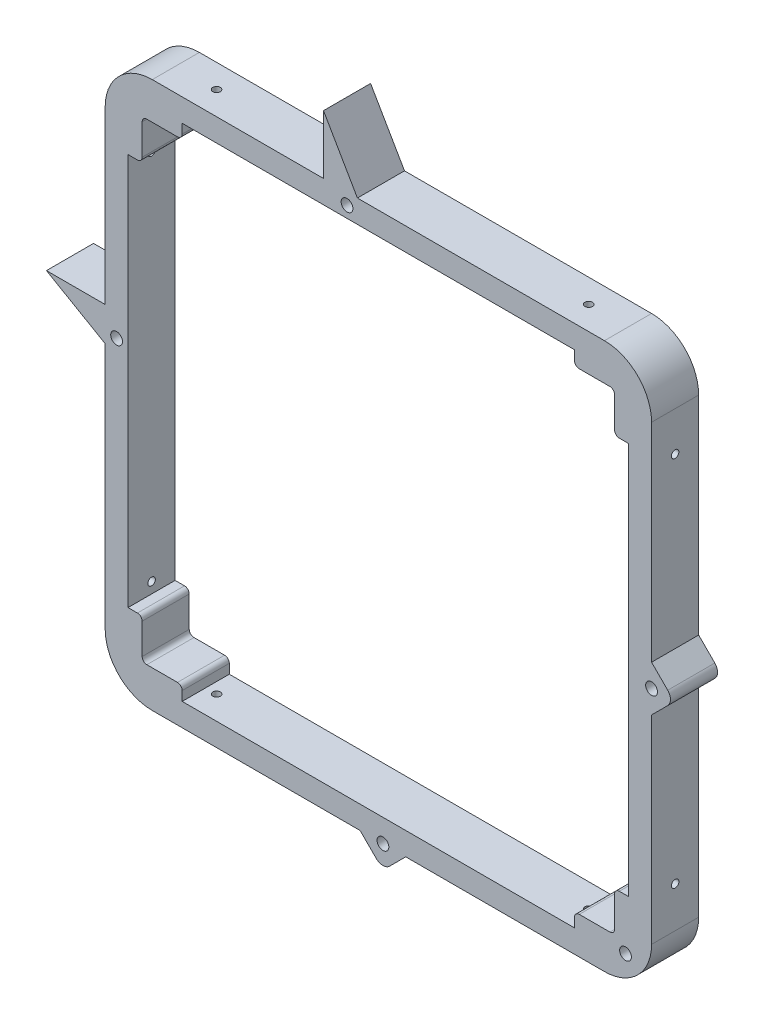
SolidWorks part; units mm, degrees
material "Nylon 101"
ref_plane "Front Plane" through (0, 0, 0) normal (0, 0, 1) x (1, 0, 0)
ref_plane "Top Plane" through (0, 0, 0) normal (0, 1, 0) x (1, 0, 0)
ref_plane "Right Plane" through (0, 0, 0) normal (1, 0, 0) x (0, 0, -1)
sketch "Sketch1" plane through (0, 0, 0) normal (0, 0, 1) x (1, 0, 0)
  line L13 (50.0019, -50.0019) -> (58, -58) construction
  line L14 (53, -41.5) -> (50.0019, -41.5)
  line L17 (41.5, -53) -> (41.5, -50.0019)
  line L18 (50.0019, -44.9586) -> (53, -44.9586)
  line L20 (53, -44.9586) -> (53, -53)
  line L23 (53, -53) -> (44.9586, -53)
  line L24 (44.9586, -53) -> (44.9586, -50.0019)
  line L25 (50.0019, -41.5) -> (50.0019, -50.0019)
  line L27 (50.0019, -50.0019) -> (41.5, -50.0019)
  line L35 (-41.5, 53) -> (41.5, 53)
  line L37 (50.0019, -50.0019) -> (50.0019, -41.5)
  line L38 (41.5, -50.0019) -> (50.0019, -50.0019)
  line L39 (53, -44.9586) -> (50.0019, -44.9586)
  line L40 (53, -53) -> (53, -44.9586)
  line L42 (44.9586, -53) -> (53, -53)
  line L43 (44.9586, -50.0019) -> (44.9586, -53)
  line L44 (53, -41.5) -> (50.0019, -41.5)
  line L45 (41.5, -53) -> (41.5, -50.0019)
  line L47 (53, -41.5) -> (53, 41.5)
  line L50 (41.5, -53) -> (-41.5, -53)
  line L52 (-41.5, -53) -> (-41.5, -50.0019)
  line L53 (-53, -41.5) -> (-50.0019, -41.5)
  line L54 (-44.96, -50.0019) -> (-44.96, -53)
  line L55 (-44.96, -53) -> (-53, -53)
  line L57 (-53, -53) -> (-53, -44.96)
  line L58 (-53, -44.96) -> (-50.0019, -44.96)
  line L59 (-41.5, -50.0019) -> (-50.0019, -50.0019)
  line L60 (-50.0019, -50.0019) -> (-50.0019, -41.5)
  line L61 (-53, -41.5) -> (-53, 41.5)
  line L63 (58, 58) -> (58, -58)
  line L65 (-50.0019, -50.0019) -> (-41.5, -50.0019)
  line L66 (-50.0019, -41.5) -> (-50.0019, -50.0019)
  line L67 (-44.96, -53) -> (-44.96, -50.0019)
  line L68 (-53, -53) -> (-44.96, -53)
  line L70 (-53, -44.96) -> (-53, -53)
  line L71 (-50.0019, -44.96) -> (-53, -44.96)
  line L72 (-41.5, -53) -> (-41.5, -50.0019)
  line L73 (-53, -41.5) -> (-50.0019, -41.5)
  line L75 (58, -58) -> (-58, -58)
  line L77 (-50.0019, -50.0019) -> (-58, -58) construction
  line L79 (-58, -58) -> (-58, 58)
  line L81 (-53, 41.5) -> (-50.0019, 41.5)
  line L82 (-41.5, 53) -> (-41.5, 50.0019)
  line L83 (-50.0019, 44.96) -> (-53, 44.96)
  line L84 (-53, 44.96) -> (-53, 53)
  line L86 (-53, 53) -> (-44.96, 53)
  line L87 (-44.96, 53) -> (-44.96, 50.0019)
  line L88 (-50.0019, 41.5) -> (-50.0019, 50.0019)
  line L89 (-50.0019, 50.0019) -> (-41.5, 50.0019)
  line L90 (-58, 58) -> (58, 58)
  line L94 (-50.0019, 50.0019) -> (-50.0019, 41.5)
  line L95 (-41.5, 50.0019) -> (-50.0019, 50.0019)
  line L96 (-53, 44.96) -> (-50.0019, 44.96)
  line L97 (-53, 53) -> (-53, 44.96)
  line L99 (-44.96, 53) -> (-53, 53)
  line L100 (-44.96, 50.0019) -> (-44.96, 53)
  line L101 (-53, 41.5) -> (-50.0019, 41.5)
  line L102 (-41.5, 53) -> (-41.5, 50.0019)
  line L106 (-50.0019, 50.0019) -> (-58, 58) construction
  line L110 (41.5, 53) -> (41.5, 50.0019)
  line L111 (53, 41.5) -> (50.0019, 41.5)
  line L112 (44.9586, 50.0019) -> (44.9586, 53)
  line L113 (44.9586, 53) -> (53, 53)
  line L115 (53, 53) -> (53, 44.96)
  line L116 (53, 44.96) -> (50.0019, 44.96)
  line L117 (41.5, 50.0019) -> (50.0019, 50.0019)
  line L118 (50.0019, 50.0019) -> (50.0019, 41.5)
  line L123 (50.0019, 50.0019) -> (41.5, 50.0019)
  line L124 (50.0019, 41.5) -> (50.0019, 50.0019)
  line L125 (44.9586, 53) -> (44.9586, 50.0019)
  line L126 (53, 53) -> (44.9586, 53)
  line L128 (53, 44.96) -> (53, 53)
  line L129 (50.0019, 44.96) -> (53, 44.96)
  line L130 (41.5, 53) -> (41.5, 50.0019)
  line L131 (53, 41.5) -> (50.0019, 41.5)
  line L135 (50.0019, 50.0019) -> (58, 58) construction
  point P2 (0, 58)
  point P4 (0, 53)
  point P6 (0, -53)
  point P7 (0, -58)
  point P10 (53, 0)
  point P11 (-53, 0)
  point P16 (-58, 0)
  point P17 (58, 0)
  dimension "D1" = 106
  dimension "D2" = 5
  dimension "D3" = 2.9981
extrude "base" add sketch "Sketch1" along normal mid plane 10 contours L20 L13 L14 L25 L18 | L13 L23 L24 L27 L17 | L13 L27 L24 L23 | L25 L13 L20 L18 | L117 L118 L116 L115 L113 L112 | L88 L89 L87 L86 L84 L83 | L59 L60 L58 L57 L55 L54 region at (51.5009, -45.0723, 0) region at (50.1156, 47.4809, 0) region at (-45.0737, -51.5009, 0) region at (-47.4809, 50.1156, 0) region at (56.3595, 0, 0)
ref_plane "Plane3" through (0, 0, 15) normal (0, 0, 1) x (1, 0, 0)
sketch "Sketch7" plane through (0, 0, 15) normal (0, 0, 1) x (1, 0, 0)
  line L0 (-41.65, 53.15) -> (41.65, 53.15)
  line L1 (41.65, 53.15) -> (41.65, 50.1519)
  line L2 (41.65, 50.1519) -> (50.1519, 50.1519)
  line L3 (50.1519, 50.1519) -> (50.1519, 41.65)
  line L4 (50.1519, 41.65) -> (53.15, 41.65)
  line L5 (53.15, 41.65) -> (53.15, -41.65)
  line L6 (53.15, -41.65) -> (50.1519, -41.65)
  line L7 (50.1519, -41.65) -> (50.1519, -50.1519)
  line L8 (50.1519, -50.1519) -> (41.65, -50.1519)
  line L9 (41.65, -50.1519) -> (41.65, -53.15)
  line L10 (41.65, -53.15) -> (-41.65, -53.15)
  line L11 (-41.65, -53.15) -> (-41.65, -50.1519)
  line L12 (-41.65, -50.1519) -> (-50.1519, -50.1519)
  line L13 (-50.1519, -50.1519) -> (-50.1519, -41.65)
  line L14 (-50.1519, -41.65) -> (-53.15, -41.65)
  line L15 (-53.15, -41.65) -> (-53.15, 41.65)
  line L16 (-53.15, 41.65) -> (-50.1519, 41.65)
  line L17 (-50.1519, 41.65) -> (-50.1519, 50.1519)
  line L18 (-50.1519, 50.1519) -> (-41.65, 50.1519)
  line L19 (-41.65, 50.1519) -> (-41.65, 53.15)
  line L21 (-41.5, 53) -> (41.5, 53) construction
  line L22 (-41.5, 53) -> (-41.5, 50.0019) construction
  line L23 (-50.0019, 50.0019) -> (-41.5, 50.0019) construction
  line L24 (-50.0019, 41.5) -> (-50.0019, 50.0019) construction
  line L25 (-53, 41.5) -> (-50.0019, 41.5) construction
  line L26 (-53, -41.5) -> (-53, 41.5) construction
  line L27 (-53, -41.5) -> (-50.0019, -41.5) construction
  line L28 (-50.0019, -50.0019) -> (-50.0019, -41.5) construction
  line L29 (-41.5, -50.0019) -> (-50.0019, -50.0019) construction
  line L30 (-41.5, -53) -> (-41.5, -50.0019) construction
  line L31 (41.5, -53) -> (-41.5, -53) construction
  line L32 (41.5, -53) -> (41.5, -50.0019) construction
  line L33 (50.0019, -41.5) -> (50.0019, -50.0019) construction
  line L34 (53, -41.5) -> (53, 41.5) construction
  line L35 (50.0019, 50.0019) -> (50.0019, 41.5) construction
  line L36 (53, 41.5) -> (50.0019, 41.5) construction
  line L37 (41.5, 50.0019) -> (50.0019, 50.0019) construction
  dimension "D1" = 0.15
  dimension "D2" = 0.15
  dimension "D3" = 0.15
  dimension "D4" = 0.15
  dimension "D5" = 0.15
  dimension "D6" = 0.15
  dimension "D7" = 0.15
  dimension "D8" = 0.15
  dimension "D9" = 0.15
  dimension "D10" = 0.15
  dimension "D11" = 0.15
  dimension "D12" = 0.15
  dimension "D13" = 0.15
  dimension "D14" = 0.15
  dimension "D15" = 0.15
  dimension "D16" = 0.15
  dimension "D17" = 0.15
ref_plane "arm plane" through (0, 0, 0) normal (0.7071, 0.7071, 0) x (0.7071, -0.7071, 0)
sketch "Sketch2" plane through (0, 0, 0) normal (0.7071, 0.7071, 0) x (0.7071, -0.7071, 0)
  line L4 (70.9255, 5) -> (82.0244, 5)
  line L5 (19.0244, 36) -> (8.0244, 47)
  line L6 (19.0244, 36) -> (8.0244, 36) construction
  line L8 (82.0244, 5) -> (82.0244, 47)
  line L9 (82.0244, 47) -> (8.0244, 47)
  line L13 (19.0244, 36) -> (70.9255, 36)
  line L14 (70.9255, 36) -> (70.9255, 5)
  dimension "D1" = 74
  dimension "D2" = 11
  dimension "D3" = 45
  dimension "D4" = 31
extrude "arm" add sketch "Sketch2" along normal mid plane 10
ref_plane "shim supports plane" through (0, 0, -5) normal (0, 0, -1) x (-1, 0, 0)
sketch "Sketch3" plane through (0, 0, 0) normal (0, 0, 1) x (1, 0, 0)
  line L1 (61.5355, -54.4645) -> (54.4645, -61.5355) construction
  line L6 (58, 58) -> (58, -50.9289) construction
  line L7 (50.9289, -58) -> (-58, -58) construction
  line L8 (9.9167, -16.9878) -> (46.6163, -53.6874) construction
  line L9 (58, -50.9289) -> (61.5355, -54.4645) construction
  line L10 (54.818, -61.8891) -> (61.8891, -54.818)
  line L11 (61.8891, -54.818) -> (58, -50.9289)
  line L12 (58, -50.9289) -> (58, -58)
  line L13 (58, -58) -> (50.9289, -58)
  line L14 (50.9289, -58) -> (54.818, -61.8891)
  dimension "D1" = 0.5
extrude "Cut-Extrude1" cut sketch "Sketch3" against normal through all
ref_plane "Plane2" through (0, 0, -5) normal (0, 0, -1) x (-1, 0, 0)
sketch "Sketch5" plane through (0, 0, -5) normal (0, 0, -1) x (-1, 0, 0)
  line L0 (-46.6163, -53.6874) -> (-43.0808, -50.1519)
  line L7 (-50.1519, -43.0808) -> (-53.6874, -46.6163)
  line L8 (-53.6874, -46.6163) -> (-53.6874, -53.6874)
  line L9 (-50.0019, -50.0019) -> (-58, -58) construction
  line L10 (-53.6874, -53.6874) -> (-46.6163, -53.6874)
  line L12 (-53.6874, -46.6163) -> (-58, -50.9289) construction
  line L14 (-50.1519, -41.65) -> (-50.1519, -50.1519) construction
  line L15 (-50.1519, -50.1519) -> (-41.65, -50.1519) construction
  line L16 (-50.1519, -43.0808) -> (-50.1519, -50.1519)
  line L17 (-50.1519, -50.1519) -> (-43.0808, -50.1519)
  dimension "D1" = 5
  dimension "D2" = 10
extrude "Boss-Extrude4" add sketch "Sketch5" along normal up to surface (31 mm away) contours L8 L10 L0 L7 | L7 L8 L10 L0 L17 L16 region at (50.1519, -53.5374, -5) up to face at (31.8021, -31.8021, -36)
extrude "clearance" cut sketch "Sketch7" against normal up to surface (20 mm away) up to face at (0, 0, -5)
sketch "Sketch10" plane through (0, 0, 0) normal (0, 1, 0) x (1, 0, 0)
  line L0 (41.65, 5) -> (41.65, -5) construction
  circle A0 centre (39.65, 0) radius 0.8
  circle A1 centre (-39.35, 0) radius 0.8
  point P5 (41.65, 0)
  dimension "D1" = 1.6
  dimension "D2" = 2
  dimension "D3" = 79
hole_wizard "M2x0.4 Tapped Hole1" positions "Sketch11" profile "Sketch12" tap size "M2x0.4" standard "ANSI Metric" end condition through all
sketch "Sketch11" plane through (0, 0, 0) normal (0, 1, 0) x (1, 0, 0)
  point P0 (-39.35, 0)
  point P2 (39.65, 0)
sketch "Sketch12" plane through (-39.35, 0, 0) normal (1, 0, 0) x (0, 0, -1)
  line L0 (0, 0) -> (0, 58)
  line L1 (0, 58) -> (0.8, 58)
  line L2 (0.8, 58) -> (0.8, 0)
  line L5 (0.8, 0) -> (0, 0)
  line L11 (0, -6.35) -> (0, 107.95) construction
  dimension "Thru Tap Drill Dia." = 1.6
  dimension "Thru Tap Drill Depth" = 58
cosmetic thread "Hole Thread1" parameters "D2"=2
cosmetic thread "Hole Thread2" parameters "D2"=2
mirror "Mirror1" about plane through (0, 0, 0) normal (0, 1, 0) of "M2x0.4 Tapped Hole1"
cosmetic thread "Hole Thread3" parameters "D2"=2
cosmetic thread "Hole Thread4" parameters "D2"=2
sketch "Sketch13" plane through (0, 0, 0) normal (1, 0, 0) x (0, 0, -1)
  line L2 (5, 41.65) -> (-5, 41.65) construction
  circle A0 centre (0, 39.65) radius 0.8
  circle A1 centre (0, -39.35) radius 0.8
  dimension "D1" = 1.6
  dimension "D3" = 79
  dimension "D2" = 2
hole_wizard "M2x0.4 Tapped Hole2" positions "Sketch14" profile "Sketch15" tap size "M2x0.4" standard "ANSI Metric" end condition through all
sketch "Sketch14" plane through (0, 0, 0) normal (1, 0, 0) x (0, 0, -1)
  point P0 (0, 39.65)
  point P3 (0, -39.35)
sketch "Sketch15" plane through (0, 39.65, 0) normal (0, 1, 0) x (0, 0, 1)
  line L0 (0, 0) -> (0, 58)
  line L1 (0, 58) -> (0.8, 58)
  line L2 (0.8, 58) -> (0.8, 0)
  line L5 (0.8, 0) -> (0, 0)
  line L11 (0, -6.35) -> (0, 107.95) construction
  dimension "Thru Tap Drill Dia." = 1.6
  dimension "Thru Tap Drill Depth" = 58
cosmetic thread "Hole Thread5" parameters "D2"=2
cosmetic thread "Hole Thread6" parameters "D2"=2
mirror "Mirror2" about plane through (0, 0, 0) normal (1, 0, 0) of "M2x0.4 Tapped Hole2"
cosmetic thread "Hole Thread7" parameters "D2"=2
cosmetic thread "Hole Thread8" parameters "D2"=2
sketch "Sketch16" plane through (0, 0, -5) normal (0, 0, -1) x (-1, 0, 0)
  line L0 (53.15, 11.65) -> (70.4705, 11.65)
  line L6 (53.15, -41.65) -> (53.15, 41.65) construction
  line L10 (-58, -58) -> (58, 58) construction
  line L18 (70.4705, 11.65) -> (53.15, 1.65)
  line L19 (53.15, 1.65) -> (53.15, 11.65)
  dimension "D1" = 20
  dimension "D2" = 10
  dimension "D3" = 30
extrude "extender" add sketch "Sketch16" along normal blind 28.6716 contours L19 L18 region at (-58.9235, 8.3167, -5)
ref_plane "Plane5" through (0, 0, -33.6716) normal (0, 0, -1) x (-1, 0, 0)
sketch "Sketch17" plane through (0, 0, -33.6716) normal (0, 0, -1) x (-1, 0, 0)
  line L2 (116.7896, 75.2896) -> (125.4499, 66.6294)
  line L4 (53.15, 1.65) -> (53.15, 11.65)
  line L5 (53.15, 11.65) -> (116.7896, 75.2896)
  line L9 (-50.9289, -58) -> (-2.1386, -9.2096) construction
  line L14 (125.4499, 66.6294) -> (70.4705, 11.65)
  line L15 (70.4705, 11.65) -> (53.15, 1.65)
  dimension "D2" = 90
extrude "angled horizontal" add sketch "Sketch17" along normal blind 10
sketch "Sketch21" plane through (0, 0, 0) normal (0, 0, 1) x (1, 0, 0)
  line L0 (-53.15, 1.65) -> (-53.15, 11.65)
  line L1 (-70.4705, 11.65) -> (-53.15, 11.65)
  line L2 (-70.4705, 11.65) -> (-53.15, 1.65)
  line L6 (-70.4705, 11.65) -> (-58, 4.4501) construction
  line L8 (3.8891, -3.8891) -> (-3.8891, 3.8891) construction
  line L9 (-11.65, 70.4705) -> (-1.65, 53.15)
  line L10 (-11.65, 70.4705) -> (-11.65, 53.15)
  line L11 (-1.65, 53.15) -> (-11.65, 53.15)
  line L12 (-53.15, 38.85) -> (-53.15, 40.45) construction
  line L14 (-53.15, 11.65) -> (-53.15, 1.65) construction
extrude "Arm Holder" add sketch "Sketch21" along normal up to surface (5 mm away) and the other way up to surface (5 mm away) up to face at (0, 0, 5) other way up to face at (-62.1568, 9.25, -5)
fillet "Fillet1" radius 1 12 edges at (50.1519, -41.65, 0) (41.65, -50.1519, 0) (-50.1519, -41.65, 0) (-41.65, -50.1519, 0) (-50.1519, 41.65, 0) (-41.65, 50.1519, 0) (41.65, 50.1519, 0) (50.1519, 41.65, 0) (50.1519, 50.1519, 0) (50.1519, -50.1519, -15.5) (-50.1519, -50.1519, 0) (-50.1519, 50.1519, 0)
fillet "Fillet2" radius 10 4 edges at (58, -58, -21) (58, 58, 0) (-58, 58, 0) (-58, -58, 0)
hole_wizard "M3x0.5 Tapped Hole2" positions "Sketch28" profile "Sketch29" tap size "M3x0.5" standard "ANSI Metric" end condition through all
sketch "Sketch28" plane through (0, 0, -47) normal (0, 0, -1) x (-1, 0, 0)
  line L1 (-57.6593, -50.5882) -> (-9.2096, -2.1386) construction
  arc A0 (-57.6593, -50.5882) -> (-50.5882, -57.6593) centre (-48, -48) ccw construction
  point P0 (-52.4654, -52.4654)
  point P11 (-55.0711, -55.0711)
  dimension "D1" = 5
  dimension "D2" = 3.685
cosmetic thread "Hole Thread13" parameters "D2"=3
sketch "Sketch29" plane through (52.4654, -52.4654, -47) normal (1, 0, 0) x (0, 1, 0)
  line L0 (0, 0) -> (0, 52)
  line L1 (0, 52) -> (1.25, 52)
  line L2 (1.25, 52) -> (1.25, 0)
  line L5 (1.25, 0) -> (0, 0)
  line L11 (0, -6.35) -> (0, 107.95) construction
  dimension "Thru Tap Drill Dia." = 2.5
  dimension "Thru Tap Drill Depth" = 52
hole_wizard "M3x0.5 Tapped Hole3" positions "Sketch36" profile "Sketch38" tap size "M3x0.5" standard "ANSI Metric"
sketch "Sketch36" plane through (0, 0, 5) normal (0, 0, 1) x (1, 0, 0)
  line L0 (-53.15, 41.65) -> (-53.15, -41.65) construction
  line L1 (-53.15, 11.65) -> (-53.15, 1.65) construction
  point P0 (-55.575, 6.65)
  point P9 (-53.15, 6.65)
  dimension "D1" = 2.425
sketch "Sketch38" plane through (-55.575, 6.65, 5) normal (1, 0, 0) x (0, -1, 0)
  line L0 (0, 0) -> (0, 30.5611)
  line L1 (0, 30.5611) -> (1.25, 29.81)
  line L2 (1.25, 29.81) -> (1.25, 0)
  line L5 (1.25, 0) -> (0, 0)
  line L10 (0, 30.5611) -> (-1.25, 29.81) construction
  line L11 (0, -6.35) -> (0, 107.95) construction
  dimension "Tap Drill Dia." = 2.5
  dimension "Tap Drill Depth" = 29.81
  dimension "Drill Angle" = 118
cosmetic thread "Hole Thread14" parameters "D1"=28.31, "D2"=3
mirror "U part of Outside arm" about plane through (0, 0, 0) normal (0.7071, 0.7071, 0) of "M3x0.5 Tapped Hole3", "angled horizontal", "extender"
cosmetic thread "Hole Thread15" parameters "D1"=28.31, "D2"=3
sketch "Sketch39" plane through (0, 0, 0) normal (0.7071, 0.7071, 0) x (0.7071, -0.7071, 0)
  line L0 (-58.068, 43.6716) -> (-135.8205, 43.6716) construction
  line L1 (-135.8205, 43.6716) -> (-131.8205, 43.6716)
  line L2 (-135.8205, 43.6716) -> (-135.8205, 33.6716)
  line L3 (-135.8205, 33.6716) -> (-131.8205, 33.6716)
  line L4 (-131.8205, 43.6716) -> (-131.8205, 33.6716)
  line L5 (-135.8205, 43.6716) -> (-131.8205, 33.6716) construction
  line L6 (-135.8205, 33.6716) -> (-131.8205, 43.6716) construction
  line L7 (-135.8205, 43.6716) -> (-135.8205, 33.6716) construction
  line L8 (-131.8205, 33.6716) -> (-121.8205, 43.6716)
  line L9 (-121.8205, 43.6716) -> (-131.8205, 43.6716)
  line L10 (-58.068, 33.6716) -> (-135.8205, 33.6716) construction
  point P0 (-133.8205, 38.6716)
  dimension "D1" = 4
  dimension "D2" = 45
extrude "Boss-Extrude18" add sketch "Sketch39" along normal up to next and the other way up to next contours L4 L1 L2 L3 | L8 L9 L4 region at (-94.6254, 94.6254, -38.6716) region at (-90.8542, 90.8542, -40.3383)
ref_plane "Plane12" through (0, 0, 0) normal (0.7071, -0.7071, 0) x (0, 0, -1)
ref_plane "Plane13" through (27.061, -27.061, 0) normal (0.7071, -0.7071, 0) x (0, 0, -1)
sketch "Sketch34" plane through (27.061, -27.061, 0) normal (0.7071, -0.7071, 0) x (0, 0, -1)
  line L0 (47, 5) -> (36, 5)
  line L1 (36, 5) -> (11, 36.8955)
  line L2 (5, 43.7544) -> (16, 43.7544)
  line L3 (22, 36.8955) -> (47, 5)
  line L4 (5, 5) -> (47, 5) construction
  line L6 (-5, 43.7544) -> (5, 43.7544) construction
  line L8 (5, 43.7544) -> (5, 36.8955)
  line L9 (5, 36.8955) -> (11, 36.8955)
  line L12 (22, 36.8955) -> (22, 43.7544)
  line L13 (22, 43.7544) -> (16, 43.7544)
  line L14 (5, 74.9533) -> (5, 7.0711) construction
  dimension "D2" = 6
extrude "Shim support arm" add sketch "Sketch34" along normal blind 6.85
sketch "Sketch35" plane through (0, 0, -5) normal (0, 0, -1) x (-1, 0, 0)
  line L7 (-62.8437, -0.9656) -> (-58, -5.8093)
  line L12 (-58, -5.8093) -> (-58, 3.878)
  line L13 (-58, -5.8093) -> (-58, 3.878) construction
  line L15 (-62.8437, -0.9656) -> (-58, 3.878) construction
  line L16 (-58, 3.878) -> (-62.8437, -0.9656)
extrude "Boss-Extrude17" add sketch "Sketch35" against normal up to surface (10 mm away) up to face at (-5.4, 55.575, 5)
mirror "Mirror4" about plane through (0, 0, 0) normal (0.7071, 0.7071, 0) of "Boss-Extrude17", "Shim support arm"
fillet "Fillet4" radius 2 8 edges at (30.5965, -23.5254, -41.5) (35.4402, -28.3691, -41.5) (28.3691, -35.4402, -41.5) (23.5254, -30.5965, -41.5) (3.3938, -55.5718, -22) (55.5718, -3.3938, -22) (0.9656, -62.8437, -8.5) (62.8437, -0.9656, -8.5)
hole_wizard "M3x0.5 Tapped Hole4" positions "Sketch40" profile "Sketch41" tap size "M3x0.5" standard "ANSI Metric" end condition through all
sketch "Sketch40" plane through (0, 0, -22) normal (0, 0, -1) x (-1, 0, 0)
  line L2 (3.878, -58) -> (48, -58) construction
  line L5 (-5.3274, -58.4819) -> (-2.3798, -61.4295) construction
  line L6 (-53.6382, -0.4838) -> (-58, 3.878) construction
  line L7 (-58, 48) -> (-58, 3.878) construction
  point P0 (-0.9656, -58)
  point P2 (-58, -0.9656)
  dimension "D1" = 3.425
  dimension "D2" = 3.425
sketch "Sketch41" plane through (0.9656, -58, -22) normal (1, 0, 0) x (0, 1, 0)
  line L0 (0, 0) -> (0, 27)
  line L1 (0, 27) -> (1.25, 27)
  line L2 (1.25, 27) -> (1.25, 0)
  line L5 (1.25, 0) -> (0, 0)
  line L11 (0, -6.35) -> (0, 107.95) construction
  dimension "Thru Tap Drill Dia." = 2.5
  dimension "Thru Tap Drill Depth" = 27
cosmetic thread "Hole Thread16" parameters "D2"=3
cosmetic thread "Hole Thread17" parameters "D2"=3
split "Split1" bodies to split 146 resulting bodies 142 split by face at (-42.9734, -42.3301, -5)
